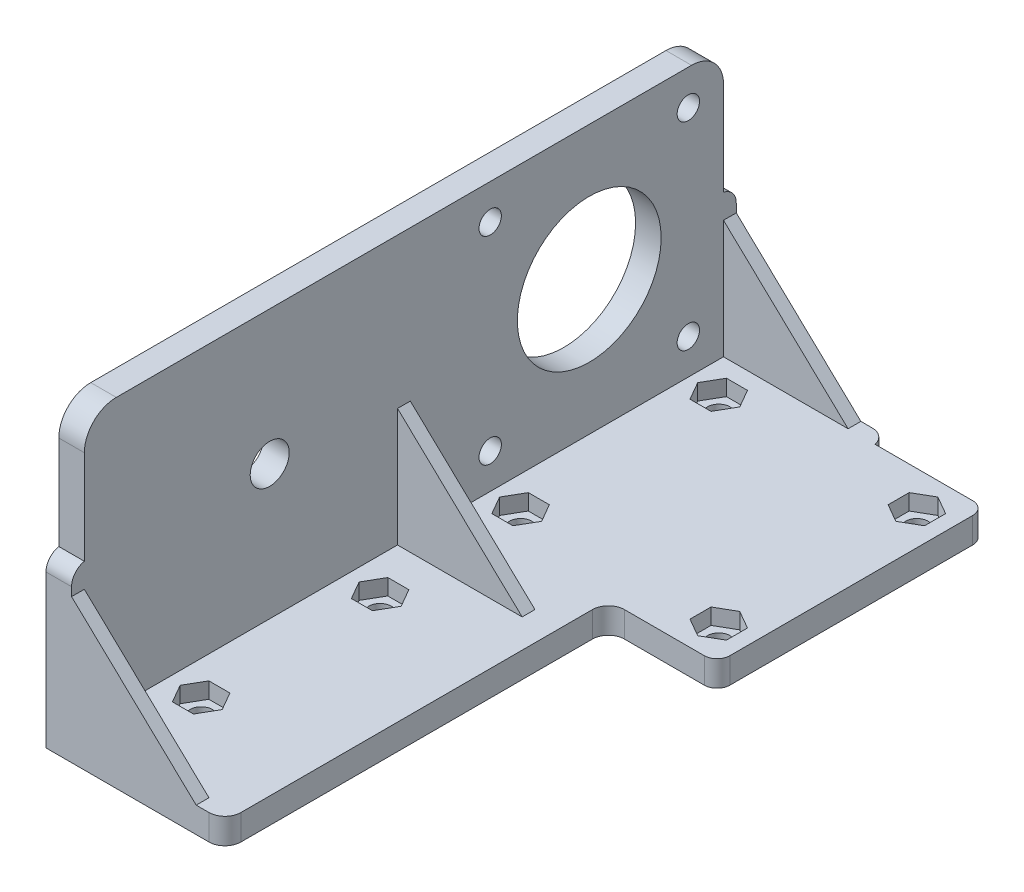
SolidWorks part; units mm, degrees
ref_plane "Front Plane" through (0, 0, 0) normal (0, 0, 1) x (1, 0, 0)
ref_plane "Top Plane" through (0, 0, 0) normal (0, 1, 0) x (1, 0, 0)
ref_plane "Right Plane" through (0, 0, 0) normal (1, 0, 0) x (0, 0, -1)
sketch "Sketch1" plane through (0, 0, 0) normal (1, 0, 0) x (0, 0, -1)
  line L0 (0, 12.7477) -> (0, 3.5) construction
  line L1 (-16, 21) -> (16, 21)
  line L2 (-21, 16) -> (-21, -21)
  line L3 (-21, -21) -> (21, -21)
  line L4 (21, 16) -> (21, -21)
  line L5 (-21, 21) -> (21, -21) construction
  line L6 (-21, -21) -> (21, 21) construction
  line L7 (-3.9174, 0) -> (-12.1376, 0) construction
  circle A0 centre (15.5, 15.5) radius 1.75
  circle A1 centre (-15.5, 15.5) radius 1.75
  circle A2 centre (15.5, -15.5) radius 1.75
  circle A3 centre (-15.5, -15.5) radius 1.75
  arc A4 (21, 16) -> (16, 21) centre (16, 16) ccw
  arc A5 (-21, 16) -> (-16, 21) centre (-16, 16) cw
  circle A6 centre (0, 0) radius 11.25
  point P0 (0, 0)
  dimension "D3" = 3.5
  dimension "D4" = 31
  dimension "D5" = 5
  dimension "D6" = 22.5
  dimension "D1" = 42
  dimension "D2" = 42
extrude "Boss-Extrude1" add sketch "Sketch1" along normal blind 2 and the other way blind 2
sketch "Sketch2" plane through (-2, 0, 0) normal (-1, 0, 0) x (0, 0, 1)
  line L1 (-21, -21) -> (21, -21)
  line L2 (-21, -21) -> (-21, -25)
  line L3 (-21, -25) -> (21, -25)
  line L4 (21, -21) -> (21, -25)
  dimension "D1" = 4
extrude "Boss-Extrude2" add sketch "Sketch2" against normal blind 45
sketch "Sketch3" plane through (0, -21, 0) normal (0, 1, 0) x (1, 0, 0)
  line L1 (37.777, 18.7715) -> (34.927, 17.126)
  line L2 (34.927, 17.126) -> (34.927, 13.8351)
  line L3 (34.927, 13.8351) -> (37.777, 12.1897)
  line L4 (37.777, 12.1897) -> (40.627, 13.8351)
  line L5 (40.627, 13.8351) -> (40.627, 17.126)
  line L6 (40.627, 17.126) -> (37.777, 18.7715)
  line L7 (40.627, -13.874) -> (37.777, -12.2285)
  line L8 (37.777, -12.2285) -> (34.927, -13.874)
  line L9 (34.927, -13.874) -> (34.927, -17.1649)
  line L10 (34.927, -17.1649) -> (37.777, -18.8103)
  line L11 (37.777, -18.8103) -> (40.627, -17.1649)
  line L12 (40.627, -17.1649) -> (40.627, -13.874)
  line L13 (10.0679, -15.5194) -> (8.4224, -12.6694)
  line L14 (8.4224, -12.6694) -> (5.1316, -12.6694)
  line L15 (5.1316, -12.6694) -> (3.4861, -15.5194)
  line L16 (3.4861, -15.5194) -> (5.1316, -18.3694)
  line L17 (5.1316, -18.3694) -> (8.4224, -18.3694)
  line L18 (8.4224, -18.3694) -> (10.0679, -15.5194)
  line L19 (10.0679, 15.4806) -> (8.4224, 18.3306)
  line L20 (8.4224, 18.3306) -> (5.1316, 18.3306)
  line L21 (5.1316, 18.3306) -> (3.4861, 15.4806)
  line L22 (3.4861, 15.4806) -> (5.1316, 12.6306)
  line L23 (5.1316, 12.6306) -> (8.4224, 12.6306)
  line L24 (8.4224, 12.6306) -> (10.0679, 15.4806)
  circle A0 centre (6.777, -15.5194) radius 1.75
  circle A1 centre (6.777, 15.4806) radius 1.75
  circle A2 centre (37.777, 15.4806) radius 1.75
  circle A3 centre (37.777, -15.5194) radius 1.75
  circle A4 centre (37.777, 15.4806) radius 2.85 construction
  circle A5 centre (37.777, -15.5194) radius 2.85 construction
  circle A6 centre (6.777, -15.5194) radius 2.85 construction
  circle A7 centre (6.777, 15.4806) radius 2.85 construction
  dimension "D1" = 3.5
  dimension "D2" = 3.5
  dimension "D3" = 3.5
  dimension "D6" = 5.7
  dimension "D7" = 5.7
  dimension "D8" = 5.7
  dimension "D9" = 5.7
  dimension "D4" = 31
  dimension "D5" = 31
sketch "Sketch7" plane through (0, 0, 21) normal (0, 0, 1) x (1, 0, 0)
  line L0 (-2, -25) -> (-2, -8.8942)
  line L1 (-2, 16) -> (-2, -25) construction
  line L2 (-2, -8.8942) -> (2, -8.8942)
  line L3 (2, 16) -> (2, -21) construction
  line L4 (2, -8.8942) -> (13.2565, -21)
  line L5 (43, -21) -> (2, -21) construction
  line L6 (13.2565, -21) -> (13.2565, -25)
  line L7 (43, -25) -> (-2, -25) construction
  line L8 (13.2565, -25) -> (-2, -25)
extrude "Boss-Extrude3" [suppressed] add sketch "Sketch7" along normal blind 2
fillet "Fillet2" [suppressed] radius 2
fillet "Fillet3" [suppressed] radius 2
mirror "Mirror2" [suppressed] about plane through (0, 0, 0) normal (0, 0, 1)
fillet "Fillet4" radius 2 2 edges at (43, -23, -21) (43, -23, 21)
extrude "Cut-Extrude1" cut sketch "Sketch3" against normal blind 10 contours A2 | A3 | A0 | A1 region at (6.777, -21, 15.5194) region at (37.777, -21, -15.4806) region at (37.777, -21, 15.5194)
extrude "Cut-Extrude2" cut sketch "Sketch3<4>" against normal blind 2.5 contours L11 L12 L7 L8 L9 L10 A3 | L17 L18 L13 L14 L15 L16 A0 | L5 L6 L1 L2 L3 L4 A2 | L23 L24 L19 L20 L21 L22 A1 region at (39.1585, -21, -17.8734) region at (40.5399, -21, 15.5194) region at (9.1698, -21, 16.9009) region at (9.1698, -21, -14.0991)
sketch "Sketch3<4>" plane through (0, -21, 0) normal (0, 1, 0) x (1, 0, 0) same geometry as "Sketch3"
sketch "Sketch10" plane through (-2, 0, 0) normal (-1, 0, 0) x (0, 0, 1)
  line L0 (16, 21) -> (21, 21)
  line L2 (79, 16) -> (79, -25)
  line L3 (79, -25) -> (21, -25)
  line L4 (21, 16) -> (21, -25)
  line L5 (74.36, 21) -> (21, -25) construction
  line L6 (79, -25) -> (25.64, 21) construction
  line L7 (21, 21) -> (74, 21)
  line L8 (16, 21) -> (21, 16)
  circle A0 centre (50, 0) radius 3.05
  arc A1 (74, 21) -> (79, 16) centre (74, 16) cw
  dimension "D2" = 5
  dimension "D3" = 6.1
  dimension "D1" = 50
extrude "Boss-Extrude4" add sketch "Sketch10" against normal blind 4
sketch "Sketch11" plane through (2, 0, 0) normal (1, 0, 0) x (0, 0, -1)
  line L0 (-21, -21) -> (-79, -21)
  line L1 (-79, -25) -> (-79, 16) construction
  line L2 (-79, -21) -> (-79, -25)
  line L3 (-21, -25) -> (-79, -25) construction
  line L4 (-79, -25) -> (-21, -25)
  line L5 (-21, -25) -> (-19, -25) construction
  line L6 (-21, -25) -> (-21, -21)
extrude "Boss-Extrude5" add sketch "Sketch11" along normal blind 24
sketch "Sketch12" plane through (0, -21, 0) normal (0, 1, 0) x (1, 0, 0)
  line L1 (10.5879, -38.0194) -> (8.9424, -35.1694)
  line L2 (8.9424, -35.1694) -> (5.6516, -35.1694)
  line L3 (5.6516, -35.1694) -> (4.0061, -38.0194)
  line L4 (4.0061, -38.0194) -> (5.6516, -40.8694)
  line L5 (5.6516, -40.8694) -> (8.9424, -40.8694)
  line L6 (8.9424, -40.8694) -> (10.5879, -38.0194)
  line L7 (10.5879, -66.0194) -> (8.9424, -63.1694)
  line L8 (8.9424, -63.1694) -> (5.6516, -63.1694)
  line L9 (5.6516, -63.1694) -> (4.0061, -66.0194)
  line L10 (4.0061, -66.0194) -> (5.6516, -68.8694)
  line L11 (5.6516, -68.8694) -> (8.9424, -68.8694)
  line L12 (8.9424, -68.8694) -> (10.5879, -66.0194)
  circle A0 centre (7.297, -38.0194) radius 1.75
  circle A1 centre (6.777, -15.5194) radius 1.75 construction
  circle A2 centre (7.297, -38.0194) radius 2.85 construction
  circle A3 centre (7.297, -66.0194) radius 1.75
  circle A4 centre (7.297, -66.0194) radius 2.85 construction
  dimension "D3" = 3.5
  dimension "D4" = 5.7
  dimension "D5" = 3.5
  dimension "D1" = 22.5
  dimension "D2" = 0.52
  dimension "D6" = 28
extrude "Cut-Extrude3" cut sketch "Sketch12" against normal blind 24 contours A0 | A3 region at (7.297, -21, 38.0194) region at (7.297, -21, 66.0194)
extrude "Cut-Extrude4" cut sketch "Sketch12<3>" against normal blind 2.5 contours L5 L6 L1 L2 L3 L4 A0 | L11 L12 L7 L8 L9 L10 A3 region at (9.6898, -21, 39.4009) region at (9.6898, -21, 67.4009)
sketch "Sketch12<3>" plane through (0, -21, 0) normal (0, 1, 0) x (1, 0, 0) same geometry as "Sketch12"
fillet "Fillet5" radius 2.5 2 edges at (26, -23, 21) (26, -23, 79)
sketch "Sketch14" plane through (0, 0, -21) normal (0, 0, -1) x (-1, 0, 0)
  line L0 (-2, -2.5) -> (-21.5, -21)
  line L1 (-2, -21) -> (-2, 16) construction
  line L2 (-41, -21) -> (-2, -21) construction
  line L6 (2, -25) -> (2, 16) construction
  line L7 (2, 1.2949) -> (2, -25)
  line L8 (2, -25) -> (-25.7162, -25)
  line L9 (-41, -25) -> (2, -25) construction
  line L11 (2, 1.2949) -> (-2, 1.2949)
  line L12 (-2, 1.2949) -> (-2, -2.5)
  line L13 (-25.7162, -25) -> (-25.7162, -21)
  line L14 (-25.7162, -21) -> (-21.5, -21)
extrude "Boss-Extrude6" add sketch "Sketch14" along normal blind 2
pattern_linear "LPattern1" count 2 spacing 51 along (0, 0, 1) of "Boss-Extrude6"
fillet "Fillet6" radius 2.5 1 edges at (25.7162, -23, -23)
fillet "Fillet7" radius 2.5 1 edges at (0, 1.2949, -23)
ref_plane "Plane1" through (0, 0, 29) normal (0, 0, 1) x (1, 0, 0)
mirror "Mirror3" about plane through (0, 0, 29) normal (0, 0, 1) of "Boss-Extrude6", "Fillet7"
sketch "Sketch15" plane through (0, -21, 0) normal (0, 1, 0) x (1, 0, 0)
  line L0 (26, -23.5) -> (26, -76.5) construction
  line L1 (26, -75.8084) -> (22.7969, -75.8084)
  line L2 (26, -75.8084) -> (26, -81)
  line L3 (26, -81) -> (22.7969, -81)
  line L4 (22.7969, -75.8084) -> (22.7969, -81)
  line L5 (21.5, -81) -> (25.7162, -81) construction
extrude "Boss-Extrude7" add sketch "Sketch15" against normal blind 4
fillet "Fillet8" radius 2.5 1 edges at (26, -23, 81)
